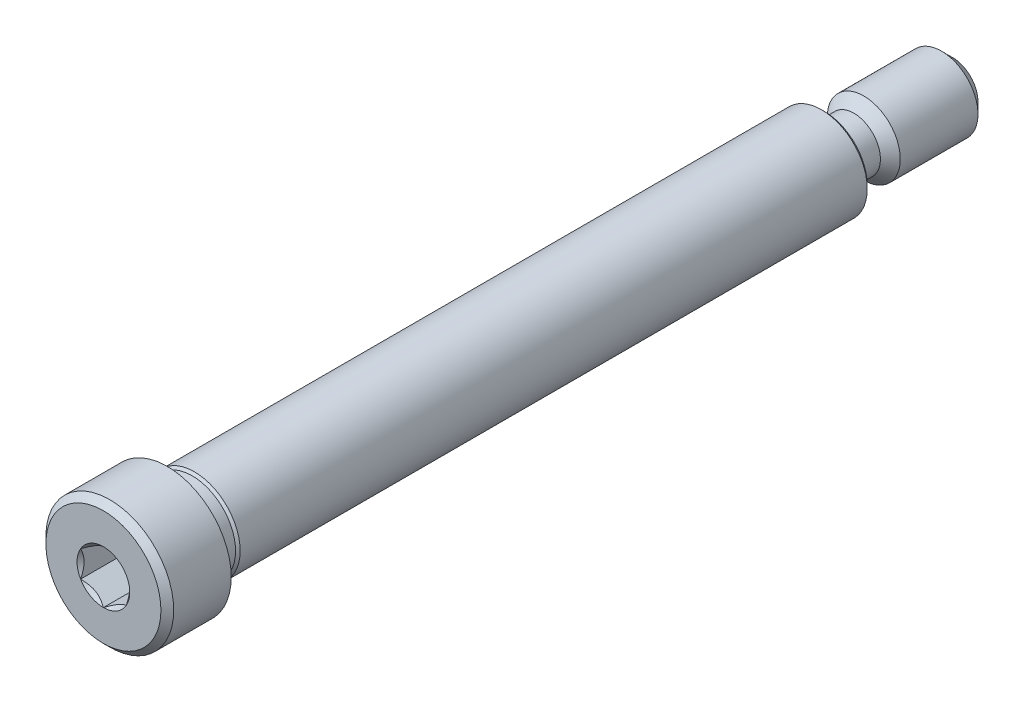
SolidWorks part; units mm, degrees
ref_plane "Front Plane" through (0, 0, 0) normal (0, 0, 1) x (1, 0, 0)
ref_plane "Top Plane" through (0, 0, 0) normal (0, 1, 0) x (1, 0, 0)
ref_plane "Right Plane" through (0, 0, 0) normal (1, 0, 0) x (0, 0, -1)
sketch "Sketch2" plane through (0, 0, 0) normal (1, 0, 0) x (0, 0, -1)
  line L0 (-36.9094, 0) -> (36.9094, 0) construction
  line L1 (-36.9094, 0) -> (-36.9094, 5.5563)
  line L2 (-36.9094, 5.5563) -> (-31.3531, 5.5563)
  line L3 (-31.3531, 5.5563) -> (-31.3531, 3.9688)
  line L4 (-31.3531, 3.9688) -> (25.7969, 3.9688)
  line L5 (25.7969, 3.175) -> (36.9094, 3.175)
  line L6 (36.9094, 3.175) -> (36.9094, 0)
  line L7 (36.83, 3.3125) -> (37.465, 2.2126) construction
  line L8 (37.465, 2.2126) -> (38.1, 3.3125) construction
  line L9 (38.1, 3.3125) -> (36.83, 3.3125) construction
  line L10 (36.9094, 3.175) -> (38.0206, 3.175) construction
  line L11 (37.465, 3.3125) -> (37.465, 3.175) construction
  line L12 (37.465, 3.175) -> (37.465, 2.3501) construction
  line L13 (37.465, 2.3501) -> (37.465, 2.2126) construction
  line L14 (37.3856, 2.3501) -> (37.5444, 2.3501)
  line L15 (36.8697, 3.2437) -> (38.0603, 3.2437)
  line L16 (37.5444, 2.3501) -> (38.0603, 3.2437)
  line L17 (37.3856, 2.3501) -> (36.8697, 3.2437)
  line L18 (36.9094, 0) -> (36.9094, -3.175) construction
  line L19 (25.7969, -3.9688) -> (25.7969, 0) construction
  line L20 (25.7969, 0) -> (25.7969, 3.9688) construction
  line L21 (-36.9094, 0) -> (-36.9094, -5.5563) construction
  point P11 (-28.9909, 3.9688)
  point P12 (33.7344, -3.175)
  point P22 (37.465, 3.2437)
  point P23 (25.2413, 0)
  point P25 (-25.2413, 0)
  point P26 (-31.3531, -5.5563)
  point P29 (25.7969, -3.9688)
  dimension "Head Height" = 5.5562
  dimension "Shoulder Diameter" = 7.9375
  dimension "Screw Size Decimal Equivalent" = 6.35
  dimension "Thread Length" = 11.1125
  dimension "Head Diameter" = 11.1125
  dimension "Undercut Length" = 2.3622
  dimension "Pitch" = 1.27
  dimension "D2" = 0.1588
  dimension "D1" = 3.175
  dimension "D3" = 11.6681
  dimension "D4" = 11.6681
  dimension "Shoulder Length" = 57.15
sketch "Sketch3" plane through (0, 0, 0) normal (0, 0, 1) x (1, 0, 0)
  line L1 (0, 2.2914) -> (-1.9844, 1.1457)
  line L2 (-1.9844, 1.1457) -> (-1.9844, -1.1457)
  line L3 (-1.9844, -1.1457) -> (0, -2.2914)
  line L4 (0, -2.2914) -> (1.9844, -1.1457)
  line L5 (1.9844, -1.1457) -> (1.9844, 1.1457)
  line L6 (1.9844, 1.1457) -> (0, 2.2914)
  circle A0 centre (0, 0) radius 1.9844 construction
  dimension "Drive Size" = 3.9688
sketch "Sketch4" plane through (0, 0, 0) normal (1, 0, 0) x (0, 0, -1)
  line L0 (-31.3531, 5.5563) -> (-36.3537, 5.5562)
  line L1 (-36.3537, 5.5562) -> (-36.9094, 5.0006)
  line L2 (-31.3531, 5.5563) -> (-31.3531, 3.9688)
  line L3 (-31.3531, 3.9688) -> (-31.1547, 3.7703)
  line L4 (-31.1547, 3.7703) -> (-29.1894, 3.7703)
  line L5 (-29.1894, 3.7703) -> (-28.9909, 3.9688)
  line L6 (-31.3531, 3.9688) -> (25.7969, 3.9688) construction
  line L7 (-36.9094, 0) -> (36.9094, 0) construction
  line L8 (-28.9909, 3.9688) -> (25.5323, 3.9688)
  line L9 (25.5323, 3.9688) -> (25.7969, 3.7042)
  line L10 (25.7969, 3.7042) -> (25.7969, 0)
  line L11 (25.7969, 3.9688) -> (25.7969, 3.7042) construction
  line L12 (25.7969, 3.7042) -> (25.7969, 3.4396) construction
  line L13 (25.7969, 3.4396) -> (25.7969, 3.175) construction
  line L14 (-36.9094, 5.0006) -> (-36.9094, 0)
  line L15 (-36.9094, 5.5563) -> (-31.3531, 5.5563) construction
  line L16 (-36.9094, 0) -> (25.7969, 0)
  dimension "D1" = 45
  dimension "D2" = 7.5406
  dimension "D3" = 45
  dimension "D4" = 45
  dimension "D5" = 10.0012
revolve "Revolve1" add sketch "Sketch4" angle 360 about L16
sketch "Sketch5" plane through (0, 0, 36.9094) normal (0, 0, 1) x (1, 0, 0)
  line L0 (1.9844, 1.1457) -> (0, 2.2914) construction
  line L1 (1.9844, -1.1457) -> (1.9844, 1.1457) construction
  line L2 (0, -2.2914) -> (1.9844, -1.1457) construction
  line L3 (-1.9844, -1.1457) -> (0, -2.2914) construction
  line L4 (-1.9844, 1.1457) -> (-1.9844, -1.1457) construction
  line L5 (0, 2.2914) -> (-1.9844, 1.1457) construction
  line L6 (1.9844, 1.1457) -> (0, 2.2914)
  line L7 (1.9844, -1.1457) -> (1.9844, 1.1457)
  line L8 (0, -2.2914) -> (1.9844, -1.1457)
  line L9 (-1.9844, -1.1457) -> (0, -2.2914)
  line L10 (-1.9844, 1.1457) -> (-1.9844, -1.1457)
  line L11 (0, 2.2914) -> (-1.9844, 1.1457)
extrude "Cut-Extrude1" cut sketch "Sketch5" against normal blind 4.1672
sketch "Sketch6" plane through (0, 0, 36.9094) normal (0, 0, 1) x (1, 0, 0)
  circle A0 centre (0, 0) radius 2.2914
extrude "Cut-Extrude4" cut sketch "Sketch6" against normal blind 4.1672 draft 45
sketch "Sketch7" plane through (0, 0, 0) normal (1, 0, 0) x (0, 0, -1)
  line L0 (25.7969, 3.175) -> (35.9569, 3.175)
  line L1 (25.7969, 3.175) -> (36.9094, 3.175) construction
  line L2 (35.9569, 3.175) -> (36.9094, 2.2225)
  line L3 (36.9094, 3.175) -> (36.9094, 0) construction
  line L4 (36.9094, 2.2225) -> (36.9094, 0)
  line L5 (36.9094, 0) -> (25.7969, 0)
  line L6 (25.7969, -3.7042) -> (25.7969, 3.7042) construction
  line L7 (25.7969, 0) -> (25.7969, 3.175)
  dimension "D1" = 45
  dimension "D2" = 0.9525
revolve "Revolve2" add sketch "Sketch7" angle 360 about L5
sketch "Sketch10" plane through (0, 0, 0) normal (1, 0, 0) x (0, 0, -1)
  line L0 (26.6605, 2.3114) -> (28.3369, 2.3114)
  line L1 (28.3369, 2.3114) -> (29.9942, 3.9688)
  line L2 (29.9942, 3.9688) -> (25.7969, 3.9688)
  line L3 (25.7969, 3.9688) -> (25.7969, 3.175)
  line L4 (25.7969, -3.7042) -> (25.7969, 3.7042) construction
  line L5 (36.9094, 0) -> (25.7969, 0) construction
  line L6 (-36.9094, 0) -> (36.9094, 0) construction
  arc A0 (25.7969, 3.175) -> (26.6605, 2.3114) centre (26.6605, 3.175) ccw
  dimension "Flat OD" = 4.6228
  dimension "Flat" = 2.54
  dimension "D3" = 45
revolve "Cut-Revolve1" cut sketch "Sketch10" angle 360 about L5
sketch "Sketch8" [suppressed] plane through (0, 0, -36.9094) normal (0, 0, -1) x (-1, 0, 0)
  circle A0 centre (0, 0) radius 3.175 construction
  circle A1 centre (0, 0) radius 3.175
curve "Helix/Spiral1" [suppressed] pitch 1.27 height 12.3825 turns 9.75
sketch "Sketch9" [suppressed] plane through (0, 0, 0) normal (1, 0, 0) x (0, 0, -1)
  line L0 (37.3856, 2.3501) -> (37.5444, 2.3501) construction
  line L1 (37.5444, 2.3501) -> (38.0603, 3.2437) construction
  line L2 (36.8697, 3.2437) -> (38.0603, 3.2437) construction
  line L3 (37.3856, 2.3501) -> (36.8697, 3.2437) construction
  line L4 (37.3856, 2.3501) -> (37.5444, 2.3501)
  line L5 (37.5444, 2.3501) -> (38.0603, 3.2437)
  line L6 (36.8697, 3.2437) -> (38.0603, 3.2437)
  line L7 (37.3856, 2.3501) -> (36.8697, 3.2437)
ref_plane "Plane1" [suppressed] through (0, 0, -28.3369) normal (0, 0, 1) x (1, 0, 0)
split "Split1" [suppressed] bodies to split 138
sweep "Cut-Sweep1" [suppressed] cut profiles "Sketch9" path "Helix/Spiral1"
combine bodies "Combine1" [suppressed] operation type add bodies to combine 141 139
sketch "Sketch11" [suppressed] plane through (0, 0, 36.9094) normal (0, 0, 1) x (1, 0, 0)
  line L0 (-0.0802, 5.5562) -> (0.0802, 5.5562)
  line L1 (0.0802, 5.5562) -> (0, 5.4173)
  line L2 (0, 0) -> (0, 5.5563) construction
  line L3 (0, 5.4173) -> (-0.0802, 5.5562)
  line L4 (0, 0) -> (5.5562, 0) construction
  circle A0 centre (0, 0) radius 5.5562 construction
  point P6 (0, 5.5562)
  dimension "D1" = 10.8347
  dimension "D2" = 60
  dimension "D3" = 0.1604
sketch "Sketch12" [suppressed] plane through (0, 0, 0) normal (1, 0, 0) x (0, 0, -1)
  line L0 (-36.9094, 5.4173) -> (-33.0775, 5.4173)
  line L1 (-32.6033, 5.8916) -> (-32.6033, 5.5563) construction
  line L2 (-36.9094, 5.5563) -> (-31.3531, 5.5563) construction
  arc A0 (-33.0775, 5.4173) -> (-32.6033, 5.8916) centre (-33.0775, 5.8916) ccw
  point P11 (-32.7422, 5.5563)
  dimension "D1" = 1.3891
sweep "Cut-Sweep2" [suppressed] cut profiles "Sketch11" path "Sketch12"
pattern_circular "CirPattern1" [suppressed] count 76 over 360 about axis through (0, 0, 36.9094) along (0, 0, -1) of bodies 143
equation "\"D2@Sketch2\" = \"Pitch@Sketch2\" / 8"
equation "\"D1@Sketch2\"=\"Pitch@Sketch2\"*2.5"
equation "\"D2@Sketch4\"=\"Shoulder Diameter@Sketch2\"*0.95"
equation "\"D5@Sketch4\"=\"Head Diameter@Sketch2\"*0.9"
equation "\"D1@Cut-Extrude1\"=\"Head Height@Sketch2\"*0.75"
equation "\"D1@Cut-Extrude4\"=\"D1@Cut-Extrude1\""
equation "\"D2@Sketch7\"=\"pitch@sketch2\"*0.75"
equation "\"D3@Helix/Spiral1\"=\"Thread Length@Sketch2\"+\"Pitch@Sketch2\""
equation "\"D4@Helix/Spiral1\"=\"Pitch@Sketch2\""
equation "\"D1@Sketch11\"=\"Head Diameter@Sketch2\"*0.975"
equation "\"D1@Sketch12\"=\"Head Height@Sketch2\"*0.25"
equation "\"D1@CirPattern1\"=\"Head Diameter@Sketch2\" * 3.14 / \"D3@Sketch11\" * 0.35"
equation "\"D3@Sketch2\"=\"Thread Length@Sketch2\"*1.05"
equation "\"D4@Sketch2\"=\"D3@Sketch2\""
